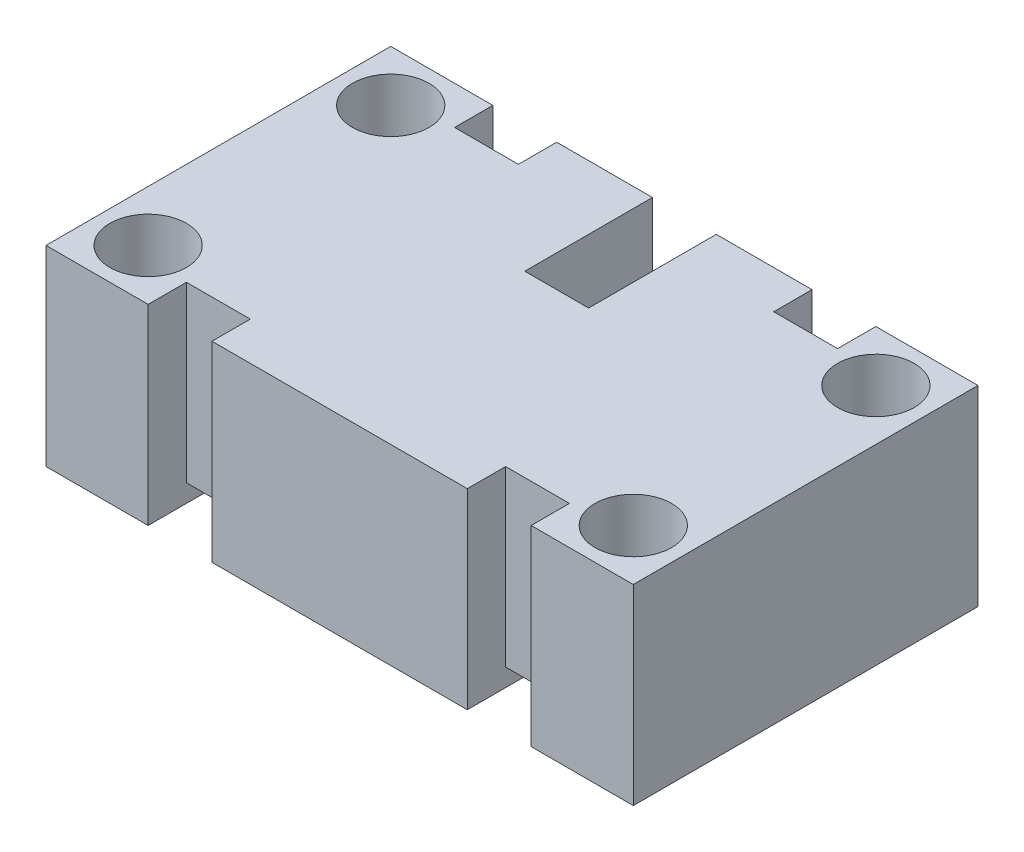
SolidWorks part; units mm, degrees
ref_plane "Front Plane" through (0, 0, 0) normal (0, 0, 1) x (1, 0, 0)
ref_plane "Top Plane" through (0, 0, 0) normal (0, 1, 0) x (1, 0, 0)
ref_plane "Right Plane" through (0, 0, 0) normal (1, 0, 0) x (0, 0, -1)
sketch "Sketch1" plane through (0, 0, 0) normal (0, 1, 0) x (1, 0, 0)
  line L0 (13.1053, 16.2424) -> (13.1053, -7.99) construction
  line L1 (-16.1047, 17.5818) -> (9.9303, 17.5818)
  line L2 (-16.1047, 17.5818) -> (-16.1047, -16.7082)
  line L3 (-16.1047, -16.7082) -> (-5.9447, -16.7082)
  line L4 (42.3153, 17.5818) -> (42.3153, -16.7082)
  line L5 (0.4053, -16.7082) -> (42.3153, -16.7082)
  line L6 (9.9303, 17.5818) -> (9.9303, 4.8818)
  line L7 (9.9303, 4.8818) -> (16.2803, 4.8818)
  line L8 (16.2803, 17.5818) -> (16.2803, 4.8818)
  line L9 (-5.9447, 17.5818) -> (0.4053, 17.5818)
  line L10 (-5.9447, 17.5818) -> (-5.9447, 13.7718)
  line L11 (-5.9447, 13.7718) -> (0.4053, 13.7718)
  line L12 (0.4053, 17.5818) -> (0.4053, 13.7718)
  line L13 (-16.1047, 0.4368) -> (42.3153, 0.4368) construction
  line L14 (25.8053, 13.7718) -> (32.1553, 13.7718)
  line L15 (32.1553, 13.7718) -> (32.1553, 17.5818)
  line L16 (32.1553, 17.5818) -> (25.8053, 17.5818)
  line L17 (25.8053, 17.5818) -> (25.8053, 13.7718)
  line L18 (-5.9447, -16.7082) -> (-5.9447, -12.8982)
  line L19 (-5.9447, -12.8982) -> (0.4053, -12.8982)
  line L20 (0.4053, -16.7082) -> (0.4053, -12.8982)
  line L21 (25.8053, -16.7082) -> (25.8053, -12.8982)
  line L22 (32.1553, -12.8982) -> (25.8053, -12.8982)
  line L23 (32.1553, -12.8982) -> (32.1553, -16.7082)
  line L24 (32.1553, -16.7082) -> (25.8053, -16.7082)
  line L25 (16.2803, 17.5818) -> (42.3153, 17.5818)
  circle A0 centre (-11.0247, 12.5018) radius 3.81
  circle A1 centre (37.2353, 12.5018) radius 3.81
  circle A2 centre (-11.0247, -11.6282) radius 3.81
  circle A3 centre (37.2353, -11.6282) radius 3.81
  circle A4 centre (-11.0247, 12.5018) radius 2.159
  circle A5 centre (-11.0247, -11.6282) radius 2.159
  circle A6 centre (37.2353, -11.6282) radius 2.159
  circle A7 centre (37.2353, 12.5018) radius 2.159
  point P25 (25.8053, 15.6768)
  point P26 (0.4053, 15.6768)
  point P27 (25.8053, 13.7718)
  point P28 (25.8053, 17.5818)
  point P29 (32.1553, 17.5818)
  point P30 (32.1553, 13.7718)
  point P44 (32.1553, -16.7082)
  point P45 (24.8596, -16.7082)
  dimension "D5" = 7.62
  dimension "D6" = 7.62
  dimension "D7" = 7.62
  dimension "D8" = 7.62
  dimension "D9" = 4.318
  dimension "D10" = 4.318
  dimension "D11" = 4.318
  dimension "D12" = 4.318
  dimension "D2" = 34.29
  dimension "D3" = 6.35
  dimension "D4" = 3.175
  dimension "D13" = 5.08
  dimension "D14" = 5.08
  dimension "D15" = 5.08
  dimension "D16" = 5.08
  dimension "D17" = 5.08
  dimension "D18" = 5.08
  dimension "D19" = 5.08
  dimension "D20" = 5.08
  dimension "D21" = 3.81
  dimension "D22" = 6.35
  dimension "D23" = 12.7
  dimension "D24" = 16.51
  dimension "D25" = 16.51
  dimension "D26" = 16.51
  dimension "D27" = 3.81
  dimension "D28" = 6.35
  dimension "D29" = 6.35
  dimension "D30" = 25.4
  dimension "D31" = 29.21
extrude "Boss-Extrude1" add sketch "Sketch1" along normal blind 19.05 contours L22 L23 L3 L4 L1 L15 L14 L17 L12 L11 L10 L2 L18 L19 L20 L21 A3 A2 A1 A0 L8 L7 L6 | L13 L2 L3 L18 L19 L20 L21 L22 L23 L4 A3 A2 region at (-11.0247, 0, -16.973) region at (13.1053, 0, 7.3919)
extrude "Boss-Extrude2" add sketch "Sketch1<3>" along normal blind 2.54 contours A0 A4 | A2 A5 | A1 A7 | A3 A6 region at (-14.7269, 0, -12.5018) region at (33.5331, 0, -12.5018) region at (-14.7269, 0, 11.6282) region at (33.5331, 0, 11.6282)
sketch "Sketch1<3>" plane through (0, 0, 0) normal (0, 1, 0) x (1, 0, 0) same geometry as "Sketch1"
sketch "Sketch2" plane through (0, 0, 16.7082) normal (0, 0, 1) x (1, 0, 0)
  line L0 (0.4053, 19.05) -> (0.4053, 0) construction
  line L1 (-5.9447, 0) -> (0.4053, 0)
  line L2 (-5.9447, 0) -> (-5.9447, 1.778)
  line L3 (-5.9447, 1.778) -> (0.4053, 1.778)
  line L4 (0.4053, 0) -> (0.4053, 1.778)
  line L5 (32.1553, 19.05) -> (32.1553, 0) construction
  line L6 (25.8053, 0) -> (32.1553, 0)
  line L7 (25.8053, 0) -> (25.8053, 1.778)
  line L8 (25.8053, 1.778) -> (32.1553, 1.778)
  line L9 (32.1553, 0) -> (32.1553, 1.778)
  dimension "D1" = 1.778
  dimension "D2" = 1.778
extrude "Cut-Extrude2" cut sketch "Sketch2" against normal through all contours L3 L2 L1 | L6 L9 L8 region at (-2.7697, 0.889, 16.7082) region at (28.9803, 0.889, 16.7082)
